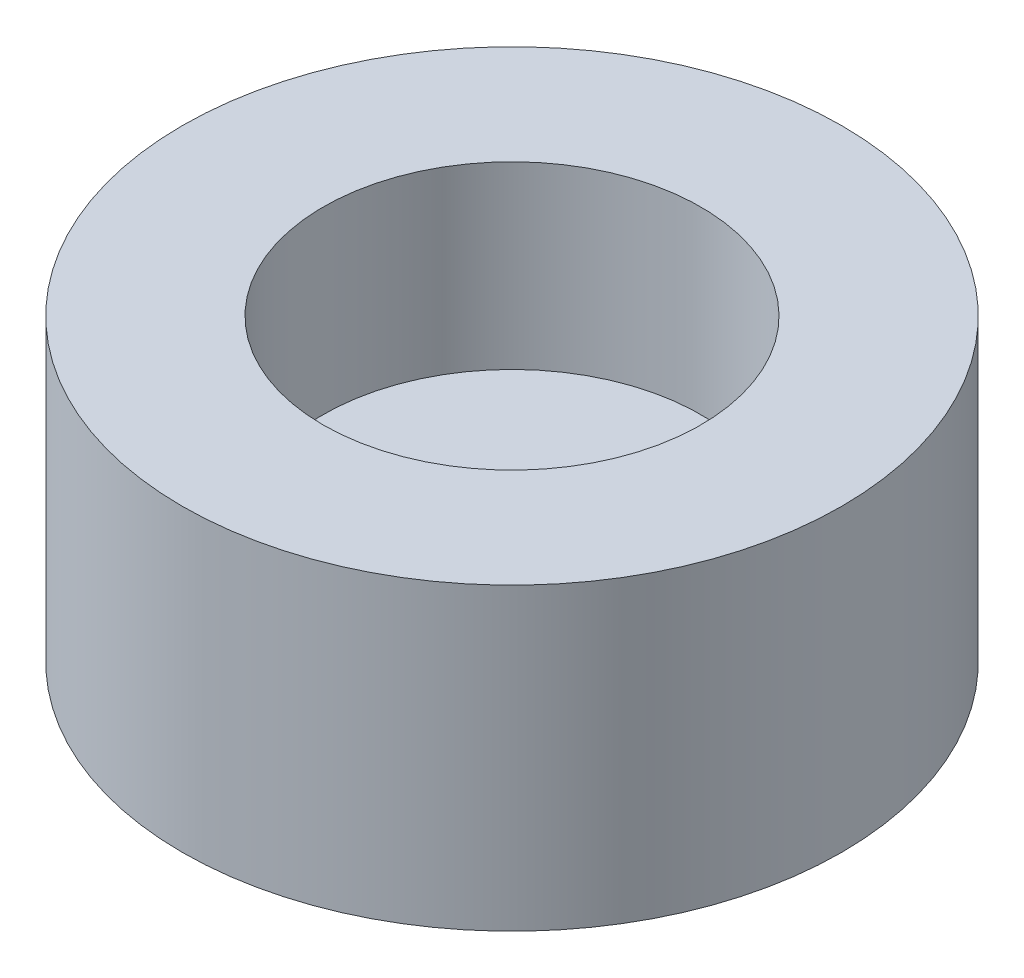
SolidWorks part; units mm, degrees
ref_plane "Front Plane" through (0, 0, 0) normal (0, 0, 1) x (1, 0, 0)
ref_plane "Top Plane" through (0, 0, 0) normal (0, 1, 0) x (1, 0, 0)
ref_plane "Right Plane" through (0, 0, 0) normal (1, 0, 0) x (0, 0, -1)
sketch "Sketch2" plane through (0, 0, 0) normal (0, 1, 0) x (1, 0, 0)
  circle A0 centre (0, 0) radius 11
  circle A1 centre (0, 0) radius 6.3
  dimension "D1" = 12.6
  dimension "D2" = 22
extrude "Boss-Extrude1" add sketch "Sketch2" along normal blind 10 contours A0
extrude "Cut-Extrude1" cut sketch "Sketch2<3>" against normal blind 6 from surface contours A1 starting at face at (0, 10, 11)
sketch "Sketch2<3>" plane through (0, 0, 0) normal (0, 1, 0) x (1, 0, 0) same geometry as "Sketch2"
